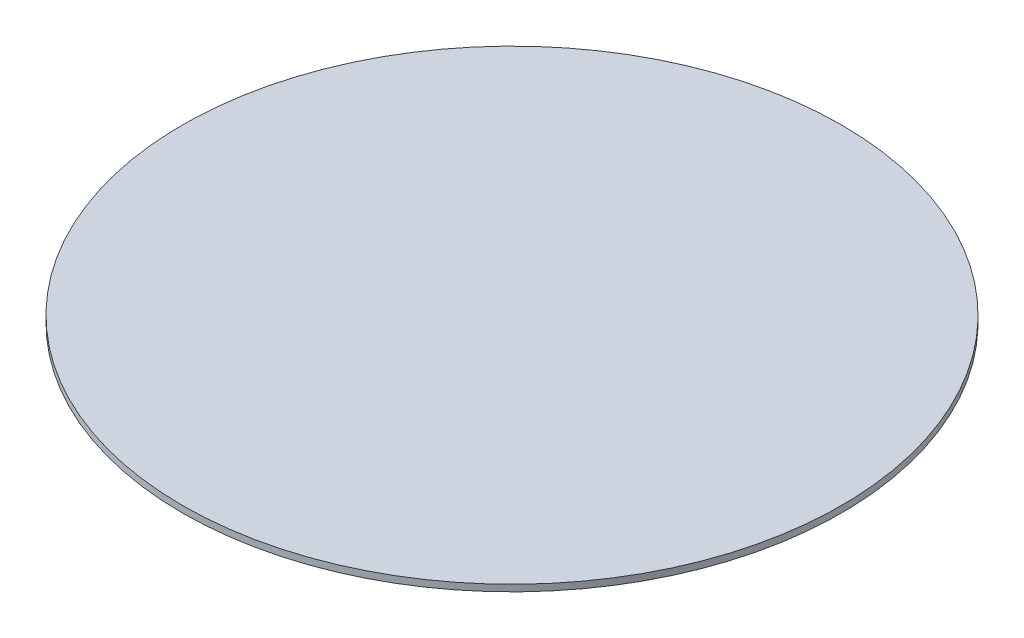
SolidWorks part; units mm, degrees
ref_plane "Front Plane" through (0, 0, 0) normal (0, 0, 1) x (1, 0, 0)
ref_plane "Top Plane" through (0, 0, 0) normal (0, 1, 0) x (1, 0, 0)
ref_plane "Right Plane" through (0, 0, 0) normal (1, 0, 0) x (0, 0, -1)
sketch "Sketch1" plane through (0, 0, 0) normal (0, 1, 0) x (1, 0, 0)
  circle A0 centre (0, 0) radius 250
extrude "Boss-Extrude1" add sketch "Sketch1" along normal blind 5
